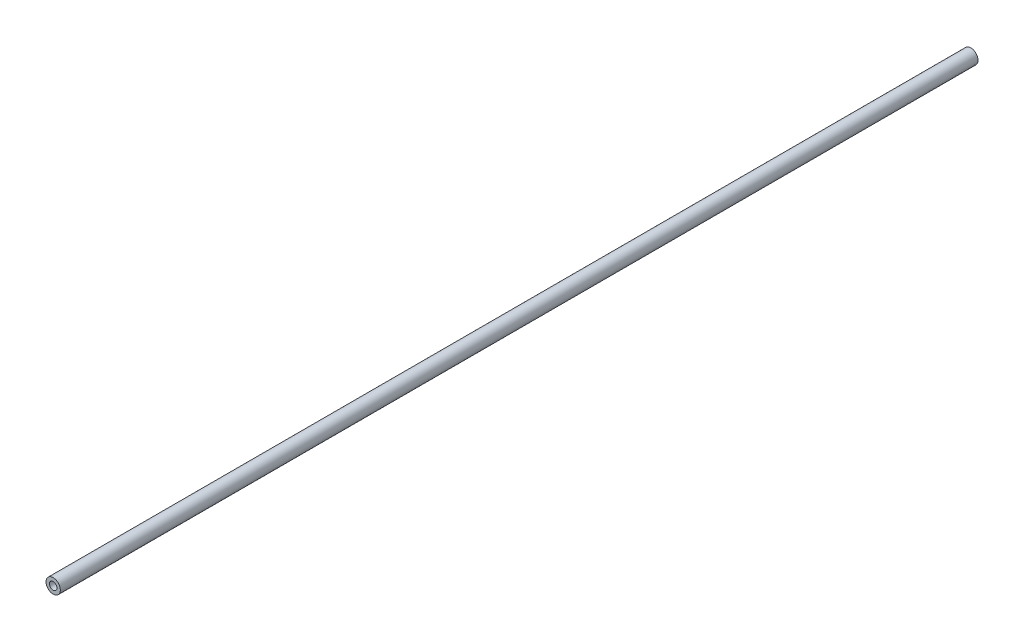
SolidWorks part; units mm, degrees
material "6061-T6 (SS)"
ref_plane "Front Plane" through (0, 0, 0) normal (0, 0, 1) x (1, 0, 0)
ref_plane "Top Plane" through (0, 0, 0) normal (0, 1, 0) x (1, 0, 0)
ref_plane "Right Plane" through (0, 0, 0) normal (1, 0, 0) x (0, 0, -1)
sketch "Sketch1" plane through (0, 0, 0) normal (0, 0, 1) x (1, 0, 0)
  circle A0 centre (0, 0) radius 2.4892
  circle A1 centre (0, 0) radius 4.7625
  dimension "D1" = 4.9784
  dimension "D2" = 9.525
extrude "Boss-Extrude1" add sketch "Sketch1" along normal mid plane 609.6
